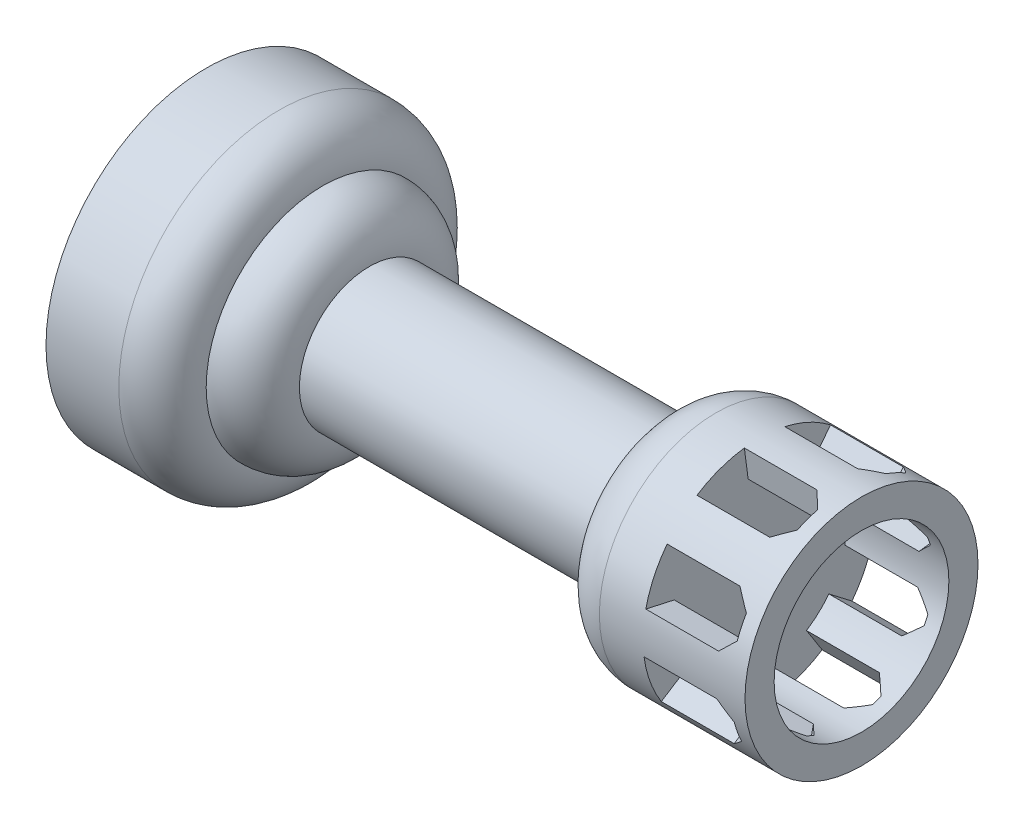
SolidWorks part; units mm, degrees
ref_plane "Спереди" through (0, 0, 0) normal (0, 0, 1) x (1, 0, 0)
ref_plane "Сверху" through (0, 0, 0) normal (0, 1, 0) x (1, 0, 0)
ref_plane "Справа" through (0, 0, 0) normal (1, 0, 0) x (0, 0, -1)
other "Configuration Table"
sketch "Эскиз1" plane through (0, 0, 0) normal (0, 1, 0) x (1, 0, 0)
  line L0 (0, 11) -> (38, 11) construction
  line L1 (0, 22) -> (5, 22)
  line L2 (0, 22) -> (0, 0)
  line L3 (0, 0) -> (5, 0)
  line L4 (5, 22) -> (5, 0)
  line L5 (5, 19) -> (8, 19)
  line L6 (5, 19) -> (5, 3)
  line L7 (5, 3) -> (8, 3)
  line L8 (8, 19) -> (8, 3)
  line L9 (8, 15.8) -> (35, 15.8)
  line L10 (8, 15.8) -> (8, 6.2)
  line L11 (8, 6.2) -> (35, 6.2)
  line L12 (35, 15.8) -> (35, 6.2)
  line L13 (35, 3) -> (38, 3)
  line L14 (35, 3) -> (35, 19)
  line L15 (35, 19) -> (38, 19)
  line L16 (38, 3) -> (38, 19)
  line L24 (38, 3) -> (45, 3)
  line L25 (38, 3) -> (38, 5)
  line L26 (38, 5) -> (45, 5)
  line L27 (45, 3) -> (45, 5)
  arc A0 (35, 3) -> (31.4652, 6.2) centre (35, 6.5523) cw
  arc A1 (8, 3) -> (11.2, 6.2) centre (8, 6.2) ccw
  arc A2 (5, 0) -> (8, 3) centre (5, 3) ccw
  dimension "D13" = 3.5523
  dimension "D14" = 7
  dimension "D15" = 3.2
  dimension "D17" = 3
  dimension "D1" = 22
  dimension "D2" = 5
  dimension "D3" = 3
  dimension "D4" = 3
  dimension "D5" = 3
  dimension "D6" = 27
  dimension "D7" = 3.2
  dimension "D8" = 3.2
  dimension "D9" = 3.2
  dimension "D10" = 3.2
  dimension "D11" = 3
  dimension "D12" = 16
  dimension "D16" = 2
revolve "Повернуть11" add sketch "Эскиз1" angle 360 about L0 region at (2.5, 0, -5.5) region at (6.5, 0, -7) region at (21.5, 0, -8.6) region at (36.5, 0, -7) region at (9.3581, 0, -4.8419) region at (33.5307, 0, -4.8526) region at (41.5, 0, -4)
sketch "Эскиз2" plane through (0, 0, 0) normal (-1, 0, 0) x (0, 0, 1)
  line L0 (50, 0) -> (-50, 0) construction
  line L1 (-22, 0) -> (0, 0) construction
  circle A0 centre (-11, 0) radius 10
  circle A1 centre (-11, 0) radius 11 construction
  dimension "D1" = 20
extrude "Вырез-Вытянуть1" cut sketch "Эскиз2" along direction (-1, 0, 0) on the side against the normal blind 2.5
sketch "Эскиз6" plane through (38, 0, 0) normal (1, 0, 0) x (0, 0, -1)
  line L0 (11, 0) -> (3.1896, 1.7315) construction
  line L1 (11, 0) -> (4.6532, 4.8701) construction
  line L2 (50, 0) -> (-50, 0) construction
  line L3 (4.6532, 4.8701) -> (6.2399, 3.6526)
  line L4 (3.1896, 1.7315) -> (5.1422, 1.2986)
  circle A2 centre (11, 0) radius 8 construction
  arc A5 (3.1896, 1.7315) -> (4.6532, 4.8701) centre (11, 0) cw
  arc A6 (5.1422, 1.2986) -> (6.2399, 3.6526) centre (11, 0) cw
  circle A8 centre (11, 0) radius 6 construction
  dimension "D1" = 12.5
  dimension "D2" = 25
extrude "Вырез-Вытянуть2" cut sketch "Эскиз6" along normal blind 6
sketch "Эскиз7" plane through (0, 0, 0) normal (1, 0, 0) x (0, 0, -1)
  line L0 (3, 0) -> (19, 0) construction
  line L1 (50, 0) -> (-50, 0) construction
  circle A0 centre (11, 0) radius 8 construction
pattern_circular "Круговой массив1" count 8 over 360 about axis through (45, 0, -11) along (-1, 0, 0) of "Вырез-Вытянуть2"
revolve "Повернуть12" add sketch "Эскиз1<12>" angle 360 about L0 region at (6.2732, 0, -1.7268)
sketch "Эскиз1<12>" plane through (0, 0, 0) normal (0, 1, 0) x (1, 0, 0) same geometry as "Эскиз1"
chamfer "Фаска4" distance 1 angle 45 2 edges at (44, 3.7611, -16.9037) (44, 0.9137, -17.9401)
chamfer "Фаска5" distance 1 angle 45 2 edges at (44, 5.5535, -15.2613) (44, 6.8341, -12.5151)
chamfer "Фаска6" distance 1 angle 45 12 edges at (44, -1.5151, -17.8341) (44, -4.2613, -16.5535) (44, -6.9401, -11.9137) (44, -5.9037, -14.7611) (44, -6.8341, -9.4849) (44, -5.5535, -6.7387) (44, -3.7611, -5.0963) (44, -0.9137, -4.0599) (44, 1.5151, -4.1659) (44, 4.2613, -5.4465) (44, 5.9037, -7.2389) (44, 6.9401, -10.0863)
sketch "Эскиз3" plane through (45, 0, 0) normal (1, 0, 0) x (0, 0, -1)
  line L0 (17, 0) -> (5, 0) construction
  line L1 (11, 0) -> (13.0706, 7.7274) construction
  line L2 (11, 0) -> (16.1423, 6.1284) construction
  line L3 (13.0706, 7.7274) -> (12.5529, 5.7956)
  line L4 (16.1423, 6.1284) -> (14.8567, 4.5963)
  line L5 (11, 0) -> (11, 8) construction
  circle A0 centre (11, 0) radius 6 construction
  circle A1 centre (11, 0) radius 6 construction
  circle A2 centre (11, 0) radius 8 construction
  arc A3 (13.0706, 7.7274) -> (16.1423, 6.1284) centre (11, 0) cw
  arc A4 (12.5529, 5.7956) -> (14.8567, 4.5963) centre (11, 0) cw
  dimension "D1" = 15
  dimension "D2" = 25
